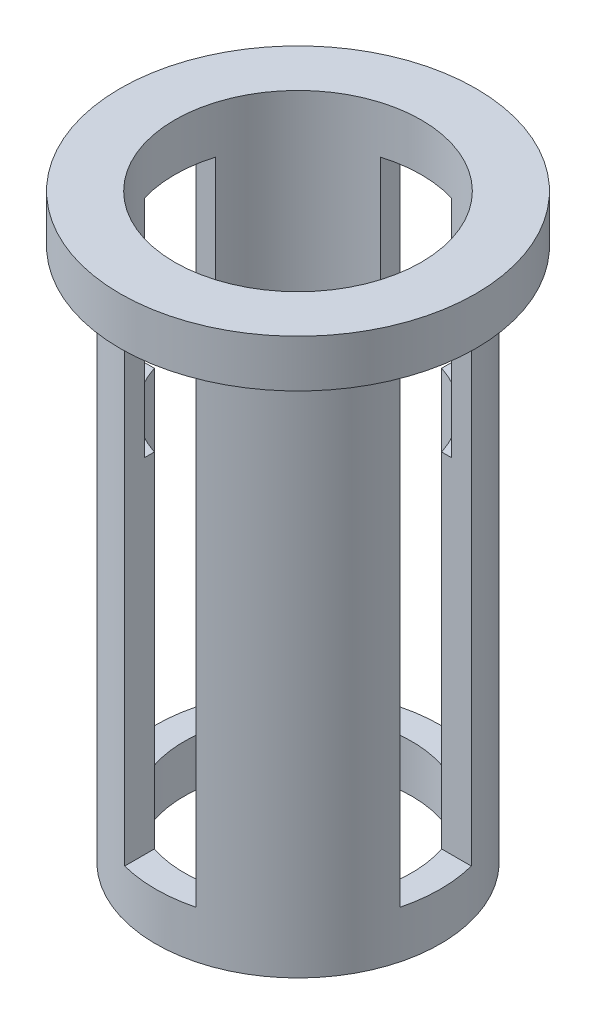
SolidWorks part; units mm, degrees
ref_plane "Front Plane" through (0, 0, 0) normal (0, 0, 1) x (1, 0, 0)
ref_plane "Top Plane" through (0, 0, 0) normal (0, 1, 0) x (1, 0, 0)
ref_plane "Right Plane" through (0, 0, 0) normal (1, 0, 0) x (0, 0, -1)
sketch "Sketch1" plane through (0, 0, 0) normal (0, 1, 0) x (1, 0, 0)
  circle A0 centre (0, 0) radius 6.604
  circle A1 centre (0, 0) radius 9.525
  dimension "D1" = 13.208
  dimension "D2" = 19.05
extrude "Boss-Extrude1" add sketch "Sketch1" along normal blind 2.54
sketch "Sketch2" plane through (0, 0, 0) normal (0, -1, 0) x (-1, 0, 0)
  circle A0 centre (0, 0) radius 6.604
  circle A1 centre (0, 0) radius 7.62
  circle A2 centre (0, 0) radius 6.604 construction
  dimension "D1" = 15.24
extrude "Boss-Extrude2" add sketch "Sketch2" along normal blind 7.62 contours A1 | A0
sketch "Sketch3" plane through (0, -7.62, 0) normal (0, -1, 0) x (-1, 0, 0)
  circle A0 centre (0, 0) radius 6.096
  circle A1 centre (0, 0) radius 7.62
  dimension "D1" = 12.192
extrude "Boss-Extrude3" add sketch "Sketch3" along normal blind 20.955
sketch "Sketch4" plane through (0, -28.575, 0) normal (0, -1, 0) x (-1, 0, 0)
  circle A0 centre (0, 0) radius 7.62 construction
  point P0 (0, -7.62)
  point P1 (0, 0)
ref_plane "Plane1" through (0, -28.575, 7.62) normal (0, 0, 1) x (1, 0, 0)
sketch "Sketch5" plane through (0, -28.575, 7.62) normal (0, 0, 1) x (1, 0, 0)
  line L1 (1.905, 2.54) -> (-1.905, 2.54)
  line L2 (1.905, 2.54) -> (1.905, 28.575)
  line L3 (1.905, 28.575) -> (-1.905, 28.575)
  line L4 (-1.905, 2.54) -> (-1.905, 28.575)
  line L5 (-7.62, 0) -> (7.62, 0) construction
  line L6 (-7.62, 28.575) -> (7.62, 28.575) construction
  dimension "D1" = 3.81
  dimension "D2" = 2.54
extrude "Cut-Extrude1" cut sketch "Sketch5" against normal through all
sketch "Sketch6" plane through (0, -28.575, 0) normal (0, -1, 0) x (-1, 0, 0)
  circle A0 centre (0, 0) radius 7.62 construction
  point P0 (-7.62, 0)
ref_plane "Plane2" through (7.62, -28.575, 0) normal (1, 0, 0) x (0, 0, -1)
sketch "Sketch7" plane through (7.62, -28.575, 0) normal (1, 0, 0) x (0, 0, -1)
  line L0 (-7.62, 0) -> (7.62, 0) construction
  line L1 (1.905, 2.54) -> (-1.905, 2.54)
  line L2 (1.905, 2.54) -> (1.905, 28.575)
  line L3 (1.905, 28.575) -> (-1.905, 28.575)
  line L4 (-1.905, 2.54) -> (-1.905, 28.575)
  line L5 (-7.378, 28.575) -> (7.378, 28.575) construction
  line L6 (0, 2.54) -> (0, 0) construction
  dimension "D1" = 3.81
  dimension "D2" = 2.54
extrude "Cut-Extrude2" cut sketch "Sketch7" against normal through all contours L2 L3 L4 L1
